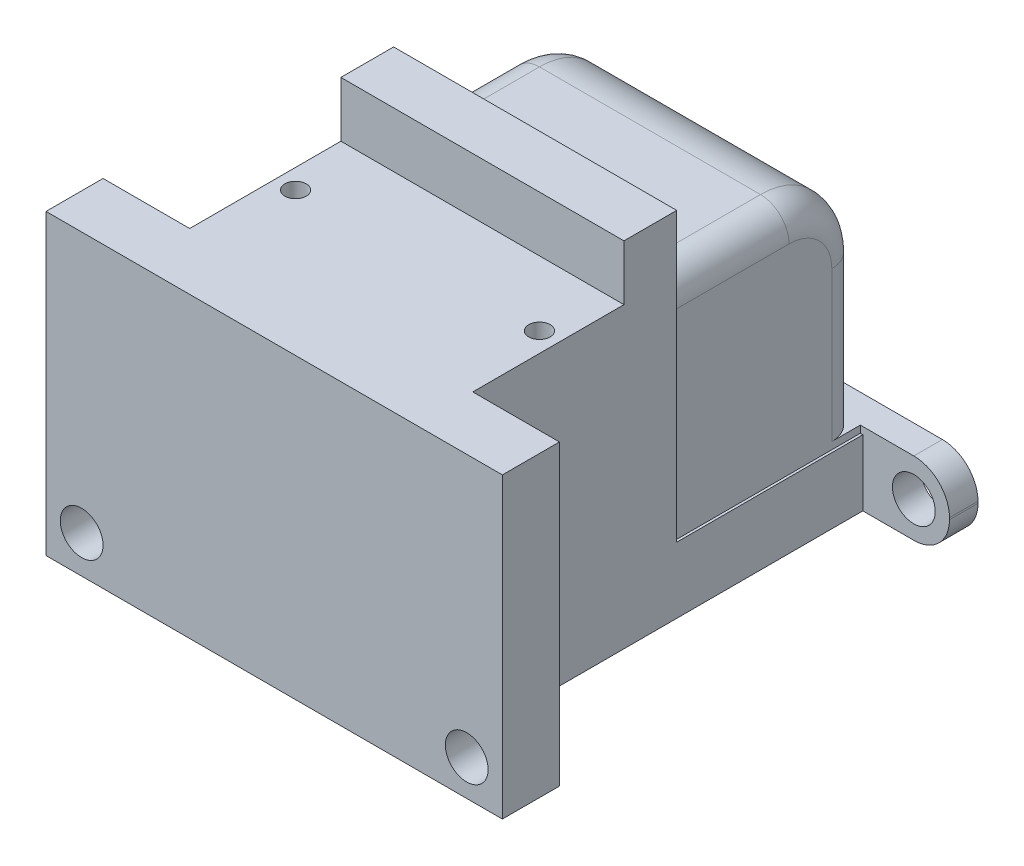
SolidWorks part; units mm, degrees
ref_plane "Plano frontal" through (0, 0, 0) normal (0, 0, 1) x (1, 0, 0)
ref_plane "Plano superior" through (0, 0, 0) normal (0, 1, 0) x (1, 0, 0)
ref_plane "Plano direito" through (0, 0, 0) normal (1, 0, 0) x (0, 0, -1)
sketch "Esboço1" plane through (0, 0, 0) normal (0, 1, 0) x (1, 0, 0)
  line L0 (-32, 29.35) -> (-19.85, 29.35)
  line L1 (-32, -33.35) -> (32, -33.35)
  line L2 (-32, -33.35) -> (-32, -25.35)
  line L3 (-32, 33.35) -> (32, 33.35)
  line L4 (32, 33.35) -> (0, 0) construction
  line L5 (-32, -33.35) -> (0, 0) construction
  line L6 (-32, 33.35) -> (0, 0) construction
  line L7 (-19.85, 29.35) -> (-19.85, -25.35)
  line L8 (-19.85, -25.35) -> (-32, -25.35)
  line L9 (32, -33.35) -> (0, 0) construction
  line L10 (6.56, 9.04) -> (6.56, 5.8113)
  line L11 (32, 29.35) -> (32, 33.35)
  line L12 (-6.56, 9.04) -> (-6.56, 5.8113)
  line L13 (-32, 29.35) -> (-32, 33.35)
  line L14 (0, 23.468) -> (0, -22.0876) construction
  line L15 (19.85, -25.35) -> (32, -25.35)
  line L16 (19.85, 29.35) -> (19.85, -25.35)
  line L17 (32, -33.35) -> (32, -25.35)
  line L18 (32, 29.35) -> (19.85, 29.35)
  point P0 (0, 0)
  point P15 (0, -33.35)
  point P23 (0, 33.35)
  dimension "D1" = 4
  dimension "D2" = 8
  dimension "D3" = 66.7
  dimension "D4" = 19.85
  dimension "D5" = 32
  dimension "D6" = 33.35
extrude "Ressalto-extrusão1" add sketch "Esboço1" along normal blind 49.55 contours L18 L11 L3 L13 L0 L7 L8 L2 L1 L17 L15 L16 region at (0, 0, 0.9044)
sketch "Esboço2" plane through (0, 49.55, 0) normal (0, 1, 0) x (1, 0, 0)
  line L0 (0, -28.9848) -> (0, -21.5278) construction
  line L1 (19.85, 3.25) -> (-19.85, 3.25)
  line L2 (-19.85, 29.35) -> (-19.85, -25.35) construction
  line L3 (-19.85, 3.25) -> (-19.85, 29.35)
  line L4 (-19.85, 29.35) -> (19.85, 29.35)
  line L5 (-19.5, 3.25) -> (-19.5, 29.35)
  line L6 (-32, 33.35) -> (32, 33.35) construction
  line L7 (-32, 29.35) -> (-19.85, 29.35) construction
  line L8 (19.5, 3.25) -> (19.5, 29.35)
  line L9 (19.85, 3.25) -> (19.85, 29.35)
  point P18 (0, 29.35)
  point P19 (0, 3.25)
  dimension "D1" = 19.5
  dimension "D2" = 30.1
extrude "Corte-extrusão1" cut sketch "Esboço2" against normal blind 8.3 contours L0 L1 L8 L4 | L1 L0 L4 L5 region at (0, 49.55, -16.3)
extrude "Corte-extrusão2" cut sketch "Esboço2<3>" against normal blind 40.3 contours L8 L1 L4 | L1 L5 L4 region at (19.675, 49.55, -16.3) region at (-19.675, 49.55, -16.3)
sketch "Esboço2<3>" plane through (0, 49.55, 0) normal (0, 1, 0) x (1, 0, 0) same geometry as "Esboço2"
sketch "Esboço3" plane through (0, 49.55, 0) normal (0, 1, 0) x (1, 0, 0)
  line L0 (32, 29.35) -> (32, 33.35)
  line L1 (32, 33.35) -> (-32, 33.35)
  line L2 (-32, 33.35) -> (-32, 29.35)
  line L3 (-32, 29.35) -> (32, 29.35)
extrude "Corte-extrusão3" cut sketch "Esboço3" against normal blind 39.3
fillet "Filete2" radius 5 4 edges at (-32, 0, -31.35) (-32, 10.25, -31.35) (32, 0, -31.35) (32, 10.25, -31.35)
fillet "Filete3" radius 10 1 edges at (0, 41.25, -29.35)
sketch "Esboço4" plane through (0, 0, -33.35) normal (0, 0, -1) x (-1, 0, 0)
  circle A0 centre (27, 5.25) radius 3
  circle A1 centre (-27, 5) radius 3
  dimension "D1" = 6
  dimension "D2" = 6
extrude "Corte-extrusão4" cut sketch "Esboço4" against normal through all
sketch "Esboço5" plane through (0, 49.55, 0) normal (0, 1, 0) x (1, 0, 0)
  line L0 (-19.85, -4.15) -> (-19.85, -25.35)
  line L1 (-32, -33.35) -> (32, -33.35) construction
  line L3 (19.85, -4.15) -> (19.85, -25.35)
  line L5 (-19.85, -4.15) -> (19.85, -4.15)
  line L7 (19.85, 3.25) -> (19.85, -25.35) construction
  line L8 (-19.85, 3.25) -> (-19.85, -25.35) construction
  line L9 (-19.85, -25.35) -> (-32, -25.35)
  line L10 (-32, -25.35) -> (-32, -33.35)
  line L11 (-32, -33.35) -> (32, -33.35)
  line L12 (32, -33.35) -> (32, -25.35)
  line L13 (32, -25.35) -> (19.85, -25.35)
  dimension "D1" = 29.2
extrude "Corte-extrusão5" cut sketch "Esboço5" against normal blind 7.75
sketch "Esboço6" plane through (0, 41.8, 0) normal (0, 1, 0) x (1, 0, 0)
  line L0 (0, -48.5216) -> (0, 47.4983) construction
  line L1 (-32, -33.35) -> (32, -33.35) construction
  circle A0 centre (17.1, -13.25) radius 1.5
  circle A1 centre (-17.1, -13.25) radius 1.5
  dimension "D1" = 3
  dimension "D2" = 17.1
  dimension "D3" = 20.1
extrude "Corte-extrusão6" cut sketch "Esboço6" against normal blind 10
fillet "Filete4" radius 4 6 edges at (-19.5, 20.75, -29.35) (-19.5, 38.3211, -26.4211) (19.5, 20.75, -29.35) (19.5, 38.3211, -26.4211) (-19.5, 41.25, -11.3) (19.5, 41.25, -11.3)
